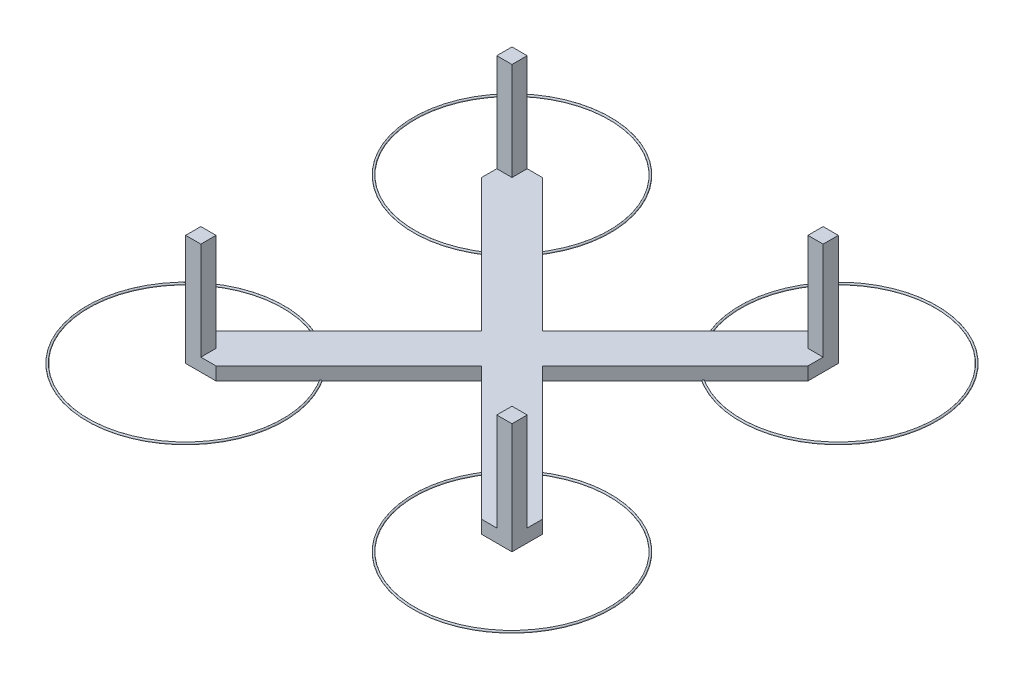
SolidWorks part; units mm, degrees
material "ABS"
ref_plane "Front Plane" through (0, 0, 0) normal (0, 0, 1) x (1, 0, 0)
ref_plane "Top Plane" through (0, 0, 0) normal (0, 1, 0) x (1, 0, 0)
ref_plane "Right Plane" through (0, 0, 0) normal (1, 0, 0) x (0, 0, -1)
sketch "Sketch1" plane through (0, 0, 0) normal (0, 1, 0) x (1, 0, 0)
  line L0 (-11.8367, 0) -> (-63.5, 51.6633)
  line L1 (-63.5, -63.5) -> (-51.6633, -63.5)
  line L2 (-63.5, -63.5) -> (-63.5, -51.6633)
  line L3 (-63.5, 63.5) -> (-51.6633, 63.5)
  line L4 (63.5, -63.5) -> (63.5, -51.6633)
  line L5 (-63.5, -63.5) -> (63.5, 63.5) construction
  line L6 (-63.5, 63.5) -> (63.5, -63.5) construction
  line L7 (0, -11.8367) -> (51.6633, -63.5)
  line L8 (0, 11.8367) -> (-51.6633, 63.5)
  line L9 (11.8367, 0) -> (63.5, -51.6633)
  line L12 (-63.5, -51.6633) -> (-11.8367, 0)
  line L13 (63.5, 51.6633) -> (11.8367, 0)
  line L16 (51.6633, 63.5) -> (63.5, 63.5)
  line L17 (63.5, 51.6633) -> (63.5, 63.5)
  line L18 (-63.5, 51.6633) -> (-63.5, 63.5)
  line L19 (51.6633, -63.5) -> (63.5, -63.5)
  line L20 (0, 11.8367) -> (51.6633, 63.5)
  line L21 (0, -11.8367) -> (-51.6633, -63.5)
  point P0 (0, 0)
extrude "Boss-Extrude1" add sketch "Sketch1" along normal blind 5.08
ref_plane "Plane3" through (0, 0, 0) normal (0, 0, -1) x (-1, 0, 0)
ref_plane "Plane1" through (0, 0, 0) normal (0.7071, 0, -0.7071) x (-0.7071, 0, -0.7071)
ref_plane "Plane2" through (0, 0, 0) normal (1, 0, 0) x (0, 0, -1)
sketch "Sketch3" plane through (0, 5.08, 0) normal (0, 1, 0) x (1, 0, 0)
  line L0 (-63.5, -63.5) -> (63.5, 63.5) construction
  line L1 (-63.5, -63.5) -> (-57.5816, -63.5)
  line L2 (-63.5, -63.5) -> (-63.5, -57.5816)
  line L3 (-63.5, -57.5816) -> (-57.5816, -57.5816)
  line L4 (-57.5816, -63.5) -> (-57.5816, -57.5816)
  line L5 (-63.5, -63.5) -> (-63.5, -51.6633) construction
  line L8 (1.9757, -1.9757) -> (-1.9757, 1.9757) construction
  line L9 (57.5816, 63.5) -> (57.5816, 57.5816)
  line L10 (63.5, 57.5816) -> (57.5816, 57.5816)
  line L11 (63.5, 63.5) -> (63.5, 57.5816)
  line L12 (63.5, 63.5) -> (57.5816, 63.5)
  line L13 (2.794, 0) -> (-2.794, 0) construction
  line L14 (-63.5, 57.5816) -> (-57.5816, 57.5816)
  line L15 (-57.5816, 63.5) -> (-57.5816, 57.5816)
  line L16 (-63.5, 63.5) -> (-57.5816, 63.5)
  line L17 (-63.5, 63.5) -> (-63.5, 57.5816)
  line L18 (0, -2.794) -> (0, 2.794) construction
  line L19 (63.5, -57.5816) -> (57.5816, -57.5816)
  line L20 (57.5816, -63.5) -> (57.5816, -57.5816)
  line L21 (63.5, -63.5) -> (57.5816, -63.5)
  line L22 (63.5, -63.5) -> (63.5, -57.5816)
extrude "Boss-Extrude2" add sketch "Sketch3" along normal blind 38.1
sketch "Sketch4" plane through (0, 0, 0) normal (0, -1, 0) x (1, 0, 0)
  circle A4 centre (-63.5, 63.5) radius 38.1
  point P12 (0, 0)
  point P14 (0, 0)
  point P21 (0, 0)
ref_plane "Plane4" through (0, 0, 0) normal (0.7071, 0, 0.7071) x (0.7071, 0, -0.7071)
sweep "Sweep11" add path "Sketch4" circular profile diameter 0.762 parameters "D3"=0.762
ref_axis "Axis1" through (0, 0, 0) along (0, 1, 0)
pattern_circular "CirPattern1" count 4 over 360 about axis through (0, 0, 0) along (0, 1, 0) of "Sweep11"
